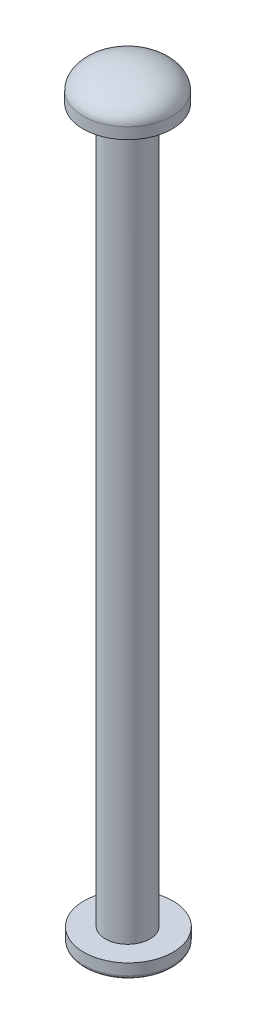
SolidWorks part; units mm, degrees
ref_plane "Front Plane" through (0, 0, 0) normal (0, 0, 1) x (1, 0, 0)
ref_plane "Top Plane" through (0, 0, 0) normal (0, 1, 0) x (1, 0, 0)
ref_plane "Right Plane" through (0, 0, 0) normal (1, 0, 0) x (0, 0, -1)
sketch "Sketch1" plane through (0, 0, 0) normal (0, 1, 0) x (1, 0, 0)
  circle A0 centre (0, 0) radius 1
  dimension "D1" = 2
extrude "Main Body of Screw" add sketch "Sketch1" along normal blind 32
sketch "Sketch2" plane through (0, 32, 0) normal (0, 1, 0) x (1, 0, 0)
  circle A0 centre (0, 0) radius 2
  dimension "D1" = 4
extrude "Top Extrude" add sketch "Sketch2" along normal blind 0.5
dome "Dome at Top" faces to dome 1 distance 1 reverse direction no elliptical dome yes face at (0, 32.5, 2) parameters "D1"=1
sketch "Sketch3" plane through (0, 0, 0) normal (0, -1, 0) x (1, 0, 0)
  circle A0 centre (0.0338, 0) radius 2
extrude "Bottom Extrude" add sketch "Sketch3" along normal blind 0.5
dome "Dome at Bottom" faces to dome 1 distance 0.5 reverse direction no elliptical dome yes face at (0.0338, -0.5, -2) parameters "D1"=0.5
